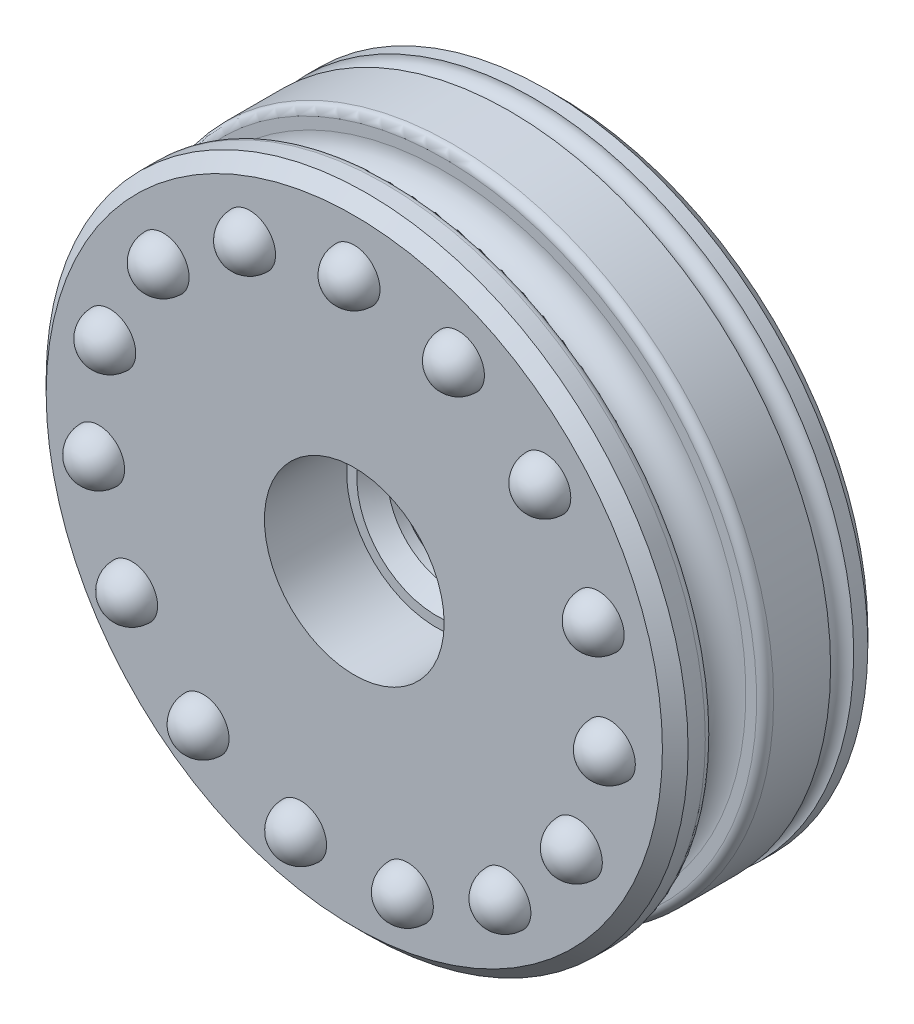
SolidWorks part; units mm, degrees
ref_plane "Front Plane" through (0, 0, 0) normal (0, 0, 1) x (1, 0, 0)
ref_plane "Top Plane" through (0, 0, 0) normal (0, 1, 0) x (1, 0, 0)
ref_plane "Right Plane" through (0, 0, 0) normal (1, 0, 0) x (0, 0, -1)
sketch "Sketch1" plane through (0, 0, 0) normal (0, 0, 1) x (1, 0, 0)
  circle A0 centre (0, 0) radius 12.5
  dimension "D1" = 25
extrude "Boss-Extrude1" add sketch "Sketch1" along normal blind 4
sketch "Sketch3" plane through (0, 0, 0) normal (1, 0, 0) x (0, 0, -1)
  line L2 (0, -12.5) -> (0, 12.5) construction
  line L3 (0, 12.5) -> (-4, 12.5) construction
  line L4 (-2.5, 11.75) -> (-2.5, 12.75)
  line L5 (-2.5, 12.75) -> (-0.5, 12.75)
  line L6 (-0.5, 12.75) -> (-0.5, 11.75)
  arc A0 (-2.5, 11.75) -> (-0.5, 11.75) centre (-1.5, 11.75) ccw
  dimension "D1" = 2
  dimension "D2" = 1.5
  dimension "D3" = 0.75
ref_axis "Axis1" through (0, 0, -0.35) along (0, 0, 1)
revolve "Cut-Revolve1" cut sketch "Sketch3" angle 360 about axis through (0, 0, -0.35) along (0, 0, 1)
sketch "Sketch2" plane through (0, 0, 4) normal (0, 0, 1) x (1, 0, 0)
  circle A0 centre (0, 0) radius 3.5
  dimension "D1" = 7
extrude "Cut-Extrude1" cut sketch "Sketch2" against normal blind 3.2
chamfer "Chamfer1" distance 0.5 angle 45 1 edges at (12.5, 0, 4)
sketch "Sketch4" plane through (0, 0, 0.8) normal (0, 0, 1) x (1, 0, 0)
  circle A0 centre (0, 0) radius 2.5
  dimension "D1" = 5
extrude "Cut-Extrude2" cut sketch "Sketch4" against normal through all
ref_axis "Axis2" through (0, 55, 4) along (0, -1, 0)
sketch "Sketch6" plane through (0, 0, 0) normal (1, 0, 0) x (0, 0, -1)
  line L0 (-4, 55) -> (-4, -55) construction
  line L1 (-4, 9) -> (-4, 11)
  line L2 (-2.5, 12.5) -> (-3.5, 12.5) construction
  arc A0 (-4, 11) -> (-4, 9) centre (-4, 10) ccw
  dimension "D1" = 2
  dimension "D2" = 2.5
revolve "Revolve1" add sketch "Sketch6" angle 360 about axis through (0, 55, 4) along (0, -1, 0)
chamfer "Chamfer2" distance 0.6 angle 45 1 edges at (2.5, 0, 0.8)
pattern_circular "CirPattern1" count 15 over 360 about axis through (0, 0, -0.35) along (0, 0, 1) of "Revolve1" reverse direction yes
mirror "Mirror2" about plane through (0, 0, 0) normal (0, 0, 1) of "Chamfer2", "Boss-Extrude1", "Cut-Extrude1", "Chamfer1", "Cut-Extrude2", "CirPattern1", "Revolve1"
sketch "Sketch7" plane through (0, 0, 0) normal (1, 0, 0) x (0, 0, -1)
  line L0 (3.5, 12.5) -> (-0.5, 12.5) construction
  line L1 (3.5, -12.5) -> (3.5, 12.5) construction
  circle A0 centre (2.5, 12.5) radius 0.45
  dimension "D1" = 0.9
  dimension "D2" = 1
revolve "Cut-Revolve3" cut sketch "Sketch7" angle 360 about axis through (0, 0, -0.35) along (0, 0, 1)
fillet "Fillet1" radius 0.33 2 edges at (12.5, 0, 2.5) (-12.5, 0, 0.5)
